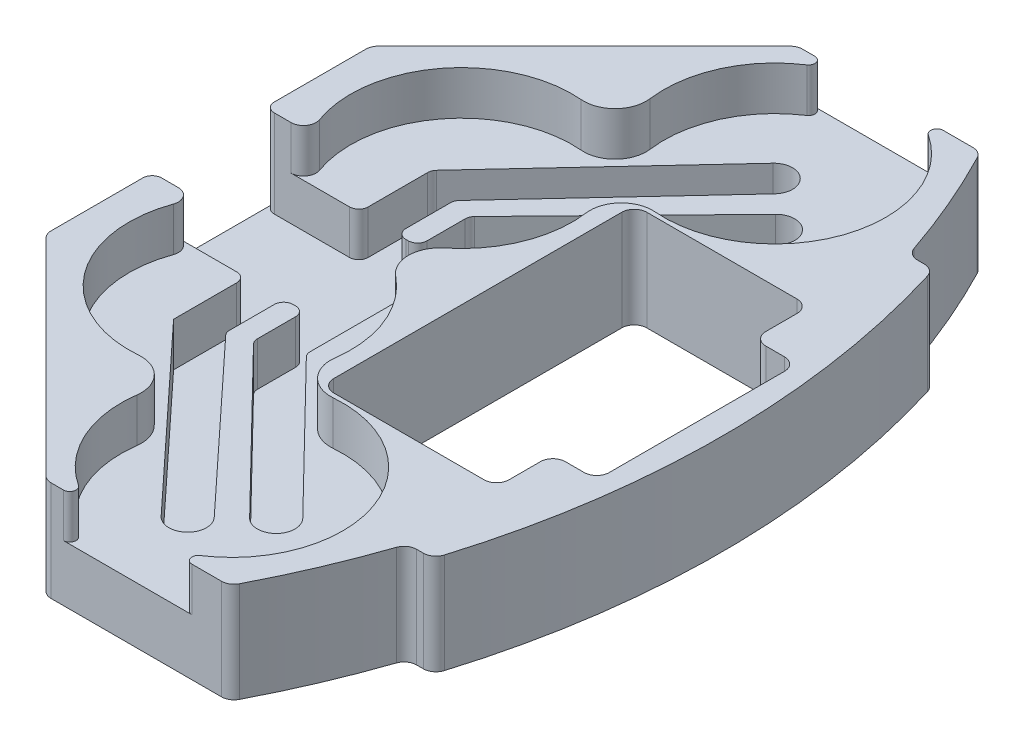
SolidWorks part; units mm, degrees
material "ABS"
ref_plane "Front Plane" through (0, 0, 0) normal (0, 0, 1) x (1, 0, 0)
ref_plane "Top Plane" through (0, 0, 0) normal (0, 1, 0) x (1, 0, 0)
ref_plane "Right Plane" through (0, 0, 0) normal (1, 0, 0) x (0, 0, -1)
sketch "Sketch1" plane through (0, 0, 0) normal (0, 1, 0) x (1, 0, 0)
  line L0 (0, 0) -> (98.9949, 98.9949) construction
  line L1 (98.9949, -98.9949) -> (0, 0) construction
  line L2 (0, 0) -> (140, 0) construction
  line L3 (34.6482, 64.3467) -> (84.1457, 113.8442) construction
  line L4 (34.6482, 64.3467) -> (64.3467, 34.6482) construction
  line L5 (84.1457, 113.8442) -> (113.8442, 84.1457) construction
  line L6 (64.3467, 34.6482) -> (113.8442, 84.1457) construction
  line L7 (34.6482, 64.3467) -> (113.8442, 84.1457) construction
  line L8 (84.1457, 113.8442) -> (64.3467, 34.6482) construction
  line L9 (64.3467, -34.6482) -> (113.8442, -84.1457) construction
  line L10 (64.3467, -34.6482) -> (34.6482, -64.3467) construction
  line L11 (113.8442, -84.1457) -> (84.1457, -113.8442) construction
  line L12 (34.6482, -64.3467) -> (84.1457, -113.8442) construction
  line L13 (64.3467, -34.6482) -> (84.1457, -113.8442) construction
  line L14 (113.8442, -84.1457) -> (34.6482, -64.3467) construction
  line L15 (50, 25.9584) -> (84.0416, 60)
  line L16 (50, 25.9584) -> (50, 0)
  line L17 (50, 0) -> (132, 0)
  line L18 (95.4594, 65.7609) -> (91.2168, 61.5183) construction
  line L19 (95.4594, 65.7609) -> (80.6102, 80.6102) construction
  line L20 (84.0416, 60) -> (117.5755, 60)
  line L22 (91.2168, 61.5183) -> (76.3675, 76.3675) construction
  line L23 (80.6102, 80.6102) -> (76.3675, 76.3675) construction
  arc A0 (98.9949, 98.9949) -> (98.9949, -98.9949) centre (0, 0) cw construction
  arc A5 (117.5755, 60) -> (132, 0) centre (0, 0) cw
  point P6 (74.2462, 74.2462)
  point P7 (74.2462, -74.2462)
  dimension "D5" = 6
  dimension "D8" = 8
  dimension "D1" = 90
  dimension "D2" = 140
  dimension "D3" = 42
  dimension "D4" = 70
  dimension "D6" = 17
  dimension "D7" = 60
  dimension "D9" = 108
  dimension "D11" = 50
extrude "Boss-Extrude1" add sketch "Sketch1" along normal blind 16
sketch "Sketch2" plane through (0, 16, 0) normal (0, 1, 0) x (1, 0, 0)
  line L1 (55, 41.8225) -> (55, 0) construction
  line L2 (91, 0) -> (119, 0) construction
  line L3 (91, 0) -> (91, 25) construction
  line L4 (91, 25) -> (119, 25) construction
  line L5 (119, 0) -> (119, 25) construction
  line L6 (0, 0) -> (135.2492, 0) construction
  line L8 (84.0416, 60) -> (50, 25.9584) construction
  circle A0 centre (97.0961, 43.356) radius 17.705
  circle A1 centre (72.705, 17.7) radius 17.705
  arc A2 (112.5444, 54.9649) -> (125.2492, 0) centre (0, 0) cw construction
  line M10 (50, 0) -> (132, 0)
  dimension "D1" = 35.41
  dimension "D4" = 91
  dimension "D2" = 25
  dimension "D3" = 28
  dimension "D5" = 55
  dimension "D6" = 35.4
  dimension "D8" = 21
extrude "Cut-Extrude4" cut sketch "Sketch2" against normal offset from surface (7 mm away) 9 contours A1 A0 M10 | A1 A0 | A0 A1 region at (97.0962, 16, -43.3561) region at (84.9006, 16, -30.528) region at (72.7049, 16, -17.7) up to face at (87.4345, 0, -29.3626)
mirror "Mirror2" about plane through (0, 0, 0) normal (0, 0, 1) of "Boss-Extrude1", "Cut-Extrude4"
fillet "Fillet3" radius 5 6 edges at (84.5956, 12.5, 30.8179) (85.2055, 12.5, 30.2381) (73.1257, 12.5, 0) (72.2843, 12.5, 0) (85.2055, 12.5, -30.2381) (84.5956, 12.5, -30.8179)
fillet "Fillet5" radius 1 4 edges at (103.1331, 12.5, 60) (91.0591, 12.5, 60) (103.1331, 12.5, -60) (91.0591, 12.5, -60)
sketch "Sketch3" plane through (0, 16, 0) normal (0, 1, 0) x (1, 0, 0)
  line L1 (93, 25) -> (121, 25)
  line L2 (93, 25) -> (93, -25)
  line L3 (93, -25) -> (121, -25)
  line L4 (121, 25) -> (121, -25)
  arc A1 (120.1047, 28.9976) -> (119.0668, -33.0014) centre (0, 0) cw construction
  dimension "D3" = 93
  dimension "D1" = 28
  dimension "D2" = 50
extrude "Cut-Extrude5" cut sketch "Sketch3" against normal up to next
sketch "Sketch6" plane through (0, 16, 0) normal (0, 1, 0) x (1, 0, 0)
  line L0 (121, -25) -> (121, 25) construction
  line L1 (121, 16) -> (128, 16)
  line L2 (121, 16) -> (121, -16)
  line L3 (121, -16) -> (128, -16)
  line L4 (128, 16) -> (128, -16)
  line L6 (93, 25) -> (93, -25) construction
  line L7 (93, 25) -> (93, -25) construction
  point P6 (93, 0)
  dimension "D1" = 32
  dimension "D2" = 16
  dimension "D3" = 35
extrude "Cut-Extrude8" cut sketch "Sketch6" against normal up to next
fillet "Fillet4" radius 2 8 edges at (121, 8, 25) (93, 8, 25) (121, 8, -25) (93, 8, -25) (121, 8, 16) (128, 8, 16) (121, 8, -16) (128, 8, -16)
sketch "Sketch4" plane through (0, 16, 0) normal (0, 1, 0) x (1, 0, 0)
  line L0 (97.0961, 43.356) -> (72.705, 17.7) construction
  line L1 (72.705, 17.7) -> (72.705, -17.7) construction
  line L2 (72.705, -17.7) -> (97.0961, -43.356) construction
  line L3 (93.4724, 46.8011) -> (100.7199, 39.911) construction
  line L4 (68.0065, 19.4101) -> (77.4035, 15.9899) construction
  line L5 (68.0065, -19.4101) -> (77.4035, -15.9899) construction
  line L6 (93.4724, -46.8011) -> (100.7199, -39.911) construction
  line L7 (93.4724, 46.8011) -> (68.0065, 19.4101) construction
  line L8 (68.0065, 19.4101) -> (68.0065, -19.4101) construction
  line L9 (68.0065, -19.4101) -> (93.4724, -46.8011) construction
  line L10 (100.7199, -39.911) -> (77.4035, -15.9899) construction
  line L11 (77.4035, -15.9899) -> (77.4035, 15.9899) construction
  line L12 (77.4035, 15.9899) -> (100.7199, 39.911) construction
  line L13 (91.2753, 48.8438) -> (65.0065, 20.5892)
  line L14 (65.0065, 20.5892) -> (65.0065, -20.5892)
  line L15 (65.0065, -20.5892) -> (91.2753, -48.8438)
  line L16 (95.6695, 44.7584) -> (71.0065, 18.231)
  line L17 (71.0065, 18.231) -> (71.0065, -18.231)
  line L18 (71.0065, -18.231) -> (95.6695, -44.7584)
  line L19 (102.8682, -37.817) -> (80.4035, -14.7697)
  line L20 (80.4035, -14.7697) -> (80.4035, 14.7697)
  line L21 (80.4035, 14.7697) -> (102.8682, 37.817)
  line L22 (98.5716, -42.005) -> (74.4035, -17.2101)
  line L23 (74.4035, -17.2101) -> (74.4035, 17.2101)
  line L24 (74.4035, 17.2101) -> (98.5716, 42.005)
  arc A0 (95.623, 25.7124) -> (106.8019, 58.1636) centre (97.0961, 43.356) ccw construction
  arc A2 (106.8019, -58.1636) -> (95.623, -25.7124) centre (97.0961, -43.356) ccw construction
  arc A3 (74.1782, 35.3436) -> (61.616, 3.8978) centre (72.705, 17.7) ccw construction
  arc A6 (61.616, -3.8978) -> (74.1782, -35.3436) centre (72.705, -17.7) ccw construction
  arc A12 (91.2753, 48.8438) -> (95.6695, 44.7584) centre (93.4724, 46.8011) cw
  arc A13 (91.2753, -48.8438) -> (95.6695, -44.7584) centre (93.4724, -46.8011) ccw
  arc A14 (102.8682, -37.817) -> (98.5716, -42.005) centre (100.7199, -39.911) cw
  arc A15 (102.8682, 37.817) -> (98.5716, 42.005) centre (100.7199, 39.911) ccw
  dimension "D2" = 3
  dimension "D1" = 10
  dimension "D3" = 70
  dimension "D4" = 70
extrude "Cut-Extrude6" cut sketch "Sketch4" against normal offset from surface (14 mm away) 2 up to face at (115.75, 0, 0)
sketch "Sketch5" plane through (0, 16, 0) normal (0, 1, 0) x (1, 0, 0)
  line L0 (50, 5) -> (80.4035, 5) construction
  line L1 (50, 25.9584) -> (50, -25.9584) construction
  line L2 (65.0065, -5) -> (50, -5) construction
  line L3 (80.4035, -14.7697) -> (80.4035, 14.7697) construction
  line L5 (50, -9) -> (80.4035, -9)
  line L7 (50, 9) -> (80.4035, 9)
  line L9 (50, -9) -> (50, 9)
  line L10 (80.4035, -9) -> (80.4035, 9)
  line L13 (50, 5) -> (80.4035, 5) construction
  line L15 (50, 25.9584) -> (50, -25.9584) construction
  point P6 (50, 0)
  point P7 (50, 0)
  dimension "D1" = 5
  dimension "D2" = 5
  dimension "D3" = 4
  dimension "D4" = 4
extrude "Cut-Extrude7" cut sketch "Sketch5" against normal offset from surface (14 mm away) 2 up to face at (115.75, 0, 0)
sketch "Sketch8" plane through (0, 16, 0) normal (0, 1, 0) x (1, 0, 0)
  line L0 (117.5755, 60) -> (107.3501, 60) construction
  line L1 (117.5755, -60) -> (107.3501, -60) construction
  line L2 (121.7935, 40) -> (125.7935, 40)
  line L3 (121.7935, -40) -> (125.7935, -40)
  arc A0 (113.2857, 60) -> (121.7935, 40) centre (0, 0) cw
  arc A1 (125.7935, -40) -> (125.7935, 40) centre (0, 0) ccw
  arc A2 (117.5755, -60) -> (117.5755, 60) centre (0, 0) ccw construction
  arc A3 (113.2857, -60) -> (121.7935, -40) centre (0, 0) ccw
  dimension "D1" = 4
  dimension "D2" = 80
  dimension "D3" = 40
extrude "Cut-Extrude10" cut sketch "Sketch8" against normal through all and the other way through all flip side to cut
fillet "Fillet6" radius 2 12 edges at (84.0416, 8, 60) (50, 8, 25.9584) (50, 8, -25.9584) (84.0416, 8, -60) (113.2857, 8, -60) (121.7935, 8, -40) (125.7935, 8, -40) (121.7935, 8, 40) (125.7935, 8, 40) (113.2857, 8, 60) (57.285, 12.5, 9) (57.285, 12.5, -9)
sketch "Sketch9" plane through (0, 0, 0) normal (0, -1, 0) x (1, 0, 0)
  circle A0 centre (120, 32) radius 1.25
  circle A1 centre (120, -32) radius 1.25
  arc A2 (126.2348, -38.5846) -> (126.2348, 38.5846) centre (0, 0) ccw construction
  dimension "D1" = 120
  dimension "D2" = 2.5
  dimension "D3" = 32
  dimension "D4" = 32
extrude "Cut-Extrude11" cut sketch "Sketch9" against normal blind 10
fillet "Fillet7" radius 1.5 15 edges at (50, 9, 9) (50, 9, -9) (74.4035, 5.5, 17.2101) (71.0065, 5.5, 18.231) (80.4035, 5.5, 14.7697) (80.4035, 5.5, -14.7697) (74.4035, 5.5, -17.2101) (65.0065, 5.5, -20.5892) (71.0065, 5.5, -18.231) (65.0065, 5.5, 9) (65.0065, 5.5, -9) (74.4035, 5.5, 9) (71.0065, 5.5, 9) (74.4035, 5.5, -9) (71.0065, 5.5, -9)
